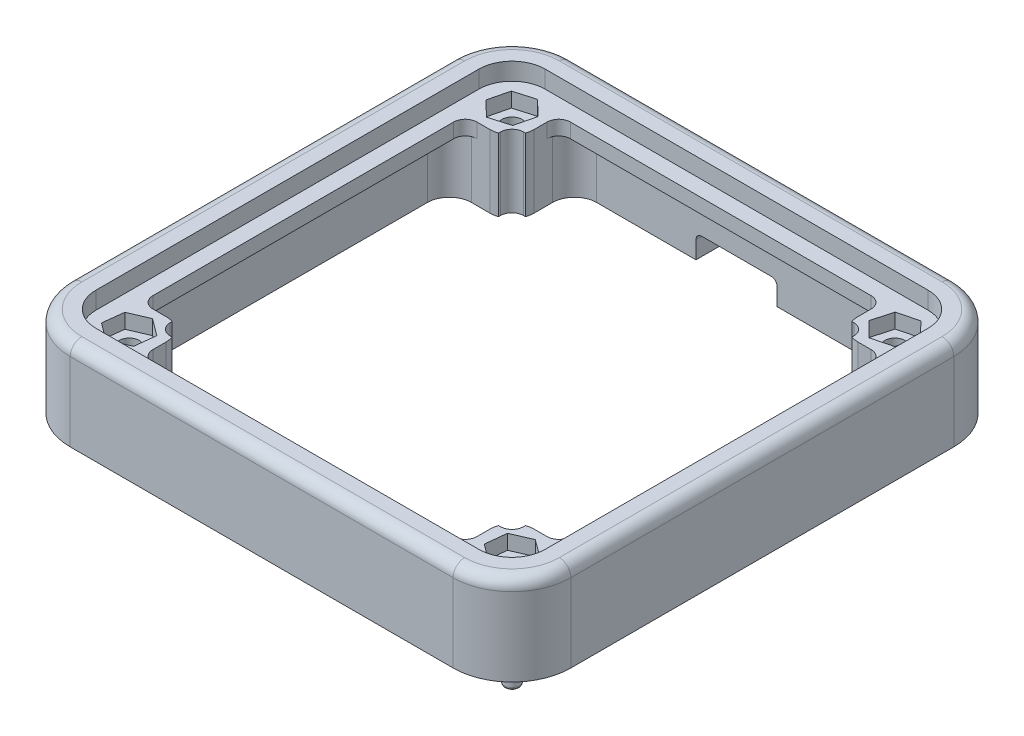
SolidWorks part; units mm, degrees
ref_plane "Front Plane" through (0, 0, 0) normal (0, 0, 1) x (1, 0, 0)
ref_plane "Top Plane" through (0, 0, 0) normal (0, 1, 0) x (1, 0, 0)
ref_plane "Right Plane" through (0, 0, 0) normal (1, 0, 0) x (0, 0, -1)
sketch "Sketch1" plane through (0, 0, 0) normal (0, 1, 0) x (1, 0, 0)
  line L0 (-43.18, 39.37) -> (-43.18, 43.18)
  line L1 (-39.37, 43.18) -> (39.37, 43.18)
  line L2 (-43.18, 39.37) -> (-43.18, -39.37)
  line L3 (-39.37, -43.18) -> (39.37, -43.18)
  line L4 (43.18, 39.37) -> (43.18, -39.37)
  line L5 (-43.18, 43.18) -> (43.18, -43.18) construction
  line L6 (-43.18, -43.18) -> (43.18, 43.18) construction
  line L7 (-43.18, 43.18) -> (-39.37, 43.18)
  line L8 (39.37, 43.18) -> (43.18, 43.18)
  line L9 (43.18, 43.18) -> (43.18, 39.37)
  line L10 (43.18, -39.37) -> (43.18, -43.18)
  line L11 (43.18, -43.18) -> (39.37, -43.18)
  line L12 (-39.37, -43.18) -> (-43.18, -43.18)
  line L13 (-43.18, -43.18) -> (-43.18, -39.37)
  point P0 (0, 0)
  dimension "D1" = 86.36
  dimension "D2" = 86.36
extrude "Boss-Extrude1" add sketch "Sketch1" along normal blind 24.9936
fillet "Fillet4" radius 2 4 edges at (-43.18, 24.9936, 0) (0, 24.9936, -43.18) (43.18, 24.9936, 0) (0, 24.9936, 43.18)
sketch "Sketch2" plane through (0, 0, -43.18) normal (0, 0, -1) x (-1, 0, 0)
  line L0 (-42.814, 8.0264) -> (35.926, 8.0264) construction
  line L1 (-7, 8.0264) -> (-7, 5.406)
  line L2 (-7, 5.406) -> (7, 5.406)
  line L3 (7, 5.406) -> (7, 8.906)
  line L4 (-42.814, 6.4516) -> (35.926, 6.4516) construction
  line L7 (-7, 8.0264) -> (-7, 13.5264)
  line L8 (-7, 13.5264) -> (7, 13.5264)
  line L9 (7, 8.906) -> (7, 13.5264)
  dimension "D1" = 5.5
  dimension "D2" = 1.5748
  dimension "D3" = 7
  dimension "D4" = 7
extrude "Cut-Extrude1" cut sketch "Sketch2" against normal blind 20
sketch "Sketch5" plane through (0, 0, -43.18) normal (0, 0, -1) x (-1, 0, 0)
  line L7 (-46.3694, 9.5021) -> (46.3694, 9.5021)
  line L8 (-46.3694, 9.5021) -> (-46.3694, -3.0563)
  line L9 (-46.3694, -3.0563) -> (46.3694, -3.0563)
  line L10 (46.3694, 9.5021) -> (46.3694, -3.0563)
  point P0 (0, 19.4522)
extrude "Cut-Extrude2" cut sketch "Sketch5" against normal blind 127
sketch "Sketch6" plane through (0, 24.9936, 0) normal (0, 1, 0) x (1, 0, 0)
  line L1 (-33.02, 38.735) -> (33.02, 38.735)
  line L2 (-38.735, 33.02) -> (-38.735, -33.02)
  line L3 (-33.02, -38.735) -> (33.02, -38.735)
  line L4 (38.735, 33.02) -> (38.735, -33.02)
  line L5 (-38.735, 38.735) -> (38.735, -38.735) construction
  line L6 (-38.735, -38.735) -> (38.735, 38.735) construction
  arc A0 (-38.735, -33.02) -> (-33.02, -38.735) centre (-33.02, -33.02) ccw
  arc A1 (33.02, -38.735) -> (38.735, -33.02) centre (33.02, -33.02) ccw
  arc A2 (33.02, 38.735) -> (38.735, 33.02) centre (33.02, 33.02) cw
  arc A3 (-33.02, 38.735) -> (-38.735, 33.02) centre (-33.02, 33.02) ccw
  point P0 (0, 0)
  dimension "D3" = 5.715
  dimension "D1" = 77.47
  dimension "D2" = 77.47
extrude "Cut-Extrude3" cut sketch "Sketch6" against normal blind 2.9972
fillet "Fillet1" radius 10.16 8 edges at (43.18, 16.2479, -43.18) (43.18, 16.2479, 43.18) (-43.18, 16.2479, 43.18) (-43.18, 16.2479, -43.18) (-42.5942, 24.4078, -42.5942) (-42.5942, 24.4078, 42.5942) (42.5942, 24.4078, 42.5942) (42.5942, 24.4078, -42.5942)
sketch "Sketch7" plane through (0, 21.9964, 0) normal (0, 1, 0) x (1, 0, 0)
  line L0 (-34.925, 27.94) -> (-31.75, 27.94)
  line L1 (33.02, 38.735) -> (-33.02, 38.735) construction
  line L2 (-24.13, 38.735) -> (24.13, 38.735)
  line L3 (-27.94, 38.735) -> (-27.94, -38.735) construction
  line L4 (-24.13, -38.735) -> (24.13, -38.735)
  line L5 (27.94, 38.735) -> (27.94, -38.735) construction
  line L6 (-27.94, 38.735) -> (27.94, -38.735) construction
  line L7 (-27.94, 31.75) -> (-27.94, 34.925)
  line L8 (-27.94, -38.735) -> (27.94, 38.735) construction
  line L9 (-38.735, 27.94) -> (38.735, 27.94) construction
  line L10 (-38.735, 24.13) -> (-38.735, -24.13)
  line L11 (-38.735, -27.94) -> (38.735, -27.94) construction
  line L12 (38.735, 24.13) -> (38.735, -24.13)
  line L13 (-38.735, 27.94) -> (38.735, -27.94) construction
  line L14 (-33.02, -38.735) -> (33.02, -38.735) construction
  line L15 (-38.735, 33.02) -> (-38.735, -33.02) construction
  line L16 (-38.735, -27.94) -> (38.735, 27.94) construction
  line L17 (27.94, 34.925) -> (27.94, 31.75)
  line L18 (31.75, 27.94) -> (34.925, 27.94)
  line L19 (34.925, -27.94) -> (31.75, -27.94)
  line L20 (27.94, -31.75) -> (27.94, -34.925)
  line L21 (-27.94, -34.925) -> (-27.94, -31.75)
  line L22 (-31.75, -27.94) -> (-34.925, -27.94)
  line L24 (33.02, 38.735) -> (-33.02, 38.735) construction
  line L25 (38.735, -33.02) -> (38.735, 33.02) construction
  line L26 (-38.735, 33.02) -> (-38.735, -33.02) construction
  circle A0 centre (-33.02, 33.02) radius 1.7488
  circle A1 centre (33.02, 33.02) radius 1.7488
  circle A2 centre (33.02, -33.02) radius 1.7488
  circle A3 centre (-33.02, -33.02) radius 1.7488
  arc A4 (24.13, 38.735) -> (27.94, 34.925) centre (24.13, 34.925) cw
  arc A5 (27.94, 31.75) -> (31.75, 27.94) centre (31.75, 31.75) ccw
  arc A6 (34.925, 27.94) -> (38.735, 24.13) centre (34.925, 24.13) cw
  arc A7 (34.925, -27.94) -> (38.735, -24.13) centre (34.925, -24.13) ccw
  arc A8 (31.75, -27.94) -> (27.94, -31.75) centre (31.75, -31.75) ccw
  arc A9 (24.13, -38.735) -> (27.94, -34.925) centre (24.13, -34.925) ccw
  arc A10 (-27.94, -34.925) -> (-24.13, -38.735) centre (-24.13, -34.925) ccw
  arc A11 (-27.94, -31.75) -> (-31.75, -27.94) centre (-31.75, -31.75) ccw
  arc A12 (-38.735, -24.13) -> (-34.925, -27.94) centre (-34.925, -24.13) ccw
  arc A13 (-34.925, 27.94) -> (-38.735, 24.13) centre (-34.925, 24.13) ccw
  arc A14 (-24.13, 38.735) -> (-27.94, 34.925) centre (-24.13, 34.925) ccw
  arc A15 (-31.75, 27.94) -> (-27.94, 31.75) centre (-31.75, 31.75) ccw
  point P0 (0, 0)
  point P1 (0, 0)
  point P7 (0, 0)
  point P8 (0, 0)
  point P41 (27.94, 27.94)
  point P50 (27.94, -27.94)
  point P59 (-27.94, -27.94)
  point P71 (-27.94, 27.94)
  dimension "D5" = 3.4976
  dimension "D8" = 3.4976
  dimension "D11" = 3.4976
  dimension "D14" = 10.795
  dimension "D15" = 3.81
  dimension "D2" = 10.795
  dimension "D3" = 5.715
  dimension "D4" = 5.715
  dimension "D6" = 5.715
  dimension "D7" = 5.715
  dimension "D9" = 5.715
  dimension "D10" = 5.715
  dimension "D12" = 5.715
  dimension "D13" = 5.715
extrude "Cut-Extrude4" cut sketch "Sketch7" against normal blind 20.7772
sketch "Sketch8" plane through (0, 21.9964, 0) normal (0, 1, 0) x (1, 0, 0)
  line L1 (-30.48, 30.48) -> (30.48, 30.48)
  line L2 (-30.48, 30.48) -> (-30.48, -30.48)
  line L3 (-30.48, -30.48) -> (30.48, -30.48)
  line L4 (30.48, 30.48) -> (30.48, -30.48)
  line L5 (-30.48, 30.48) -> (30.48, -30.48) construction
  line L6 (-30.48, -30.48) -> (30.48, 30.48) construction
  point P1 (0, 0)
  dimension "D1" = 60.96
  dimension "D2" = 60.96
extrude "Cut-Extrude5" cut sketch "Sketch8" against normal blind 20.7772
sketch "Sketch9" plane through (0, 9.5021, 0) normal (0, -1, 0) x (1, 0, 0)
  line L0 (0, 38.735) -> (0, -38.735) construction
  line L1 (-24.13, 38.735) -> (24.13, 38.735) construction
  line L2 (7, -38.735) -> (-7, -38.735) construction
  line L3 (-38.735, -24.13) -> (-38.735, 24.13) construction
  line L4 (-38.735, 0) -> (38.735, 0) construction
  line L5 (38.735, 24.13) -> (38.735, -24.13) construction
  line L6 (-43.18, -33.02) -> (-43.18, 33.02) construction
  line L7 (-33.02, 43.18) -> (33.02, 43.18) construction
  circle A0 centre (-38.1, 38.1) radius 1.27
  circle A1 centre (38.1, 38.1) radius 1.27
  circle A2 centre (-38.1, -38.1) radius 1.27
  circle A3 centre (38.1, -38.1) radius 1.27
  dimension "D3" = 2.54
  dimension "D1" = 5.08
  dimension "D2" = 5.08
extrude "Boss-Extrude2" add sketch "Sketch9" along normal blind 2.54
fillet "Fillet2" radius 0.508 4 edges at (-38.1, 6.9621, 36.83) (-38.1, 6.9621, -36.83) (38.1, 6.9621, -39.37) (38.1, 6.9621, 39.37)
fillet "Fillet3" radius 0.508 4 edges at (38.1, 9.5021, -36.83) (38.1, 9.5021, 39.37) (-38.1, 9.5021, -36.83) (-38.1, 9.5021, 39.37)
fillet "Fillet5" radius 2 4 edges at (-30.48, 15.7493, 30.48) (30.48, 15.7493, 30.48) (30.48, 15.7493, -30.48) (-30.48, 15.7493, -30.48)
sketch "Sketch10" plane through (0, 21.9964, 0) normal (0, 1, 0) x (1, 0, 0)
  line L1 (-38.79, 38.79) -> (38.79, 38.79)
  line L2 (-38.79, 38.79) -> (-38.79, -38.79)
  line L3 (-38.79, -38.79) -> (38.79, -38.79)
  line L4 (38.79, 38.79) -> (38.79, -38.79)
  line L5 (-38.79, 38.79) -> (38.79, -38.79) construction
  line L6 (-38.79, -38.79) -> (38.79, 38.79) construction
  line L7 (-36, 36) -> (36, 36)
  line L8 (-36, 36) -> (-36, -36)
  line L9 (-36, -36) -> (36, -36)
  line L10 (36, 36) -> (36, -36)
  line L11 (-36, 36) -> (36, -36) construction
  line L12 (-36, -36) -> (36, 36) construction
  arc A0 (33.02, -41.18) -> (41.18, -33.02) centre (33.02, -33.02) ccw construction
  point P0 (0, 0)
  point P9 (0, 0)
  dimension "D1" = 72
extrude "Boss-Extrude3" add sketch "Sketch10" against normal blind 2.5
fillet "Fillet6" radius 2 8 edges at (27.7852, 20.7464, -36) (36, 20.7464, -27.7852) (36, 20.7464, 27.7852) (27.7852, 20.7464, 36) (-27.7852, 20.7464, 36) (-36, 20.7464, 27.7852) (-36, 20.7464, -27.7852) (-27.7852, 20.7464, -36)
sketch "Sketch11" plane through (0, 21.9964, 0) normal (0, 1, 0) x (1, 0, 0)
  line L1 (-29.6799, -31.5798) -> (-32.5972, -29.4074)
  line L2 (-32.5972, -29.4074) -> (-35.9372, -30.8475)
  line L3 (-35.9372, -30.8475) -> (-36.3601, -34.4602)
  line L4 (-36.3601, -34.4602) -> (-33.4428, -36.6326)
  line L5 (-33.4428, -36.6326) -> (-30.1028, -35.1925)
  line L6 (-30.1028, -35.1925) -> (-29.6799, -31.5798)
  line L7 (-29.5266, 34.033) -> (-32.1506, 36.5519)
  line L8 (-32.1506, 36.5519) -> (-35.644, 35.5389)
  line L9 (-35.644, 35.5389) -> (-36.5134, 32.007)
  line L10 (-36.5134, 32.007) -> (-33.8894, 29.4881)
  line L11 (-33.8894, 29.4881) -> (-30.396, 30.5011)
  line L12 (-30.396, 30.5011) -> (-29.5266, 34.033)
  line L13 (36.5453, 33.9156) -> (34.0071, 36.5208)
  line L14 (34.0071, 36.5208) -> (30.4817, 35.6252)
  line L15 (30.4817, 35.6252) -> (29.4947, 32.1244)
  line L16 (29.4947, 32.1244) -> (32.0329, 29.5192)
  line L17 (32.0329, 29.5192) -> (35.5583, 30.4148)
  line L18 (35.5583, 30.4148) -> (36.5453, 33.9156)
  line L19 (36.3502, -31.5572) -> (33.4183, -29.4046)
  line L20 (33.4183, -29.4046) -> (30.0881, -30.8674)
  line L21 (30.0881, -30.8674) -> (29.6898, -34.4828)
  line L22 (29.6898, -34.4828) -> (32.6217, -36.6354)
  line L23 (32.6217, -36.6354) -> (35.9519, -35.1726)
  line L24 (35.9519, -35.1726) -> (36.3502, -31.5572)
  circle A0 centre (-33.02, -33.02) radius 3.15 construction
  circle A1 centre (-33.02, 33.02) radius 3.15 construction
  circle A2 centre (33.02, 33.02) radius 3.15 construction
  circle A3 centre (33.02, -33.02) radius 3.15 construction
  dimension "D1" = 6.3
  dimension "D2" = 6.3
  dimension "D3" = 6.3
  dimension "D4" = 6.3
extrude "Cut-Extrude6" cut sketch "Sketch11" against normal blind 2.54
fillet "Fillet7" radius 1 2 edges at (-7, 13.5264, -40.9575) (7, 13.5264, -40.9575)
